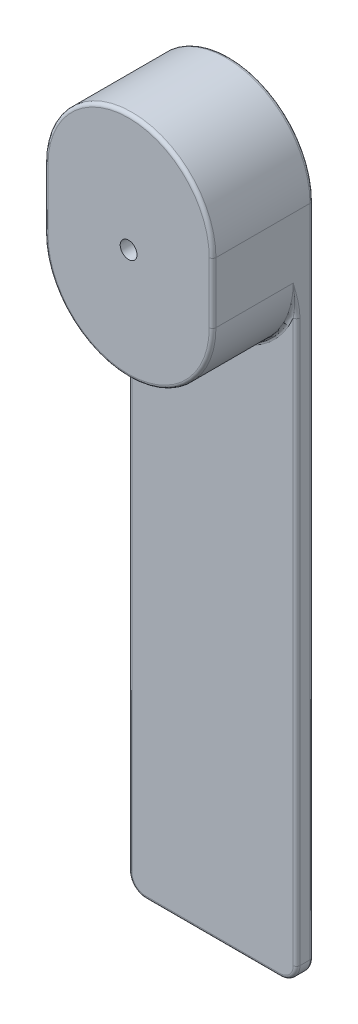
SolidWorks part; units mm, degrees
ref_plane "Front Plane" through (0, 0, 0) normal (0, 0, 1) x (1, 0, 0)
ref_plane "Top Plane" through (0, 0, 0) normal (0, 1, 0) x (1, 0, 0)
ref_plane "Right Plane" through (0, 0, 0) normal (1, 0, 0) x (0, 0, -1)
sketch "Sketch2" plane through (0, 0, 0) normal (0, 0, 1) x (1, 0, 0)
  line L2 (-50, 200) -> (-50, -200)
  line L3 (-50, -200) -> (50, -200)
  line L4 (50, 200) -> (50, -200)
  line L5 (-50, 200) -> (50, -200) construction
  line L6 (-50, -200) -> (50, 200) construction
  circle A1 centre (0, 180) radius 5
  arc A2 (-50, 200) -> (50, 200) centre (0, 200) cw
  arc A3 (-50, 163.8888) -> (50, 163.8888) centre (0, 163.8888) ccw
  point P0 (0, 0)
  point P12 (0, 0)
  dimension "D4" = 10
  dimension "D1" = 400
  dimension "D3" = 100
extrude "Boss-Extrude1" add sketch "Sketch2" along normal blind 10 contours A3 L2 L3 L4 region at (0, -37.4987, 0)
extrude "Boss-Extrude2" add sketch "Sketch2<3>" along normal blind 60 contours L2 A3 L4 A2 A1 region at (0, 248.311, 0)
sketch "Sketch2<3>" plane through (0, 0, 0) normal (0, 0, 1) x (1, 0, 0) same geometry as "Sketch2"
fillet "Fillet1" radius 2 12 edges at (0, 250, 0) (50, 181.9444, 60) (-50, 181.9444, 60) (0, 250, 60) (0, 113.8888, 60) (0, 113.8888, 10) (0, -200, 10) (-50, -18.0556, 10) (50, -18.0556, 10) (-50, 0, 0) (0, -200, 0) (50, 0, 0)
fillet "Fillet2" radius 10 6 edges at (-49.4142, -199.4142, 0.5858) (-49.4142, -199.4142, 9.4142) (49.4142, -199.4142, 0.5858) (49.4142, -199.4142, 9.4142) (50, -200, 5) (-50, -200, 5)
